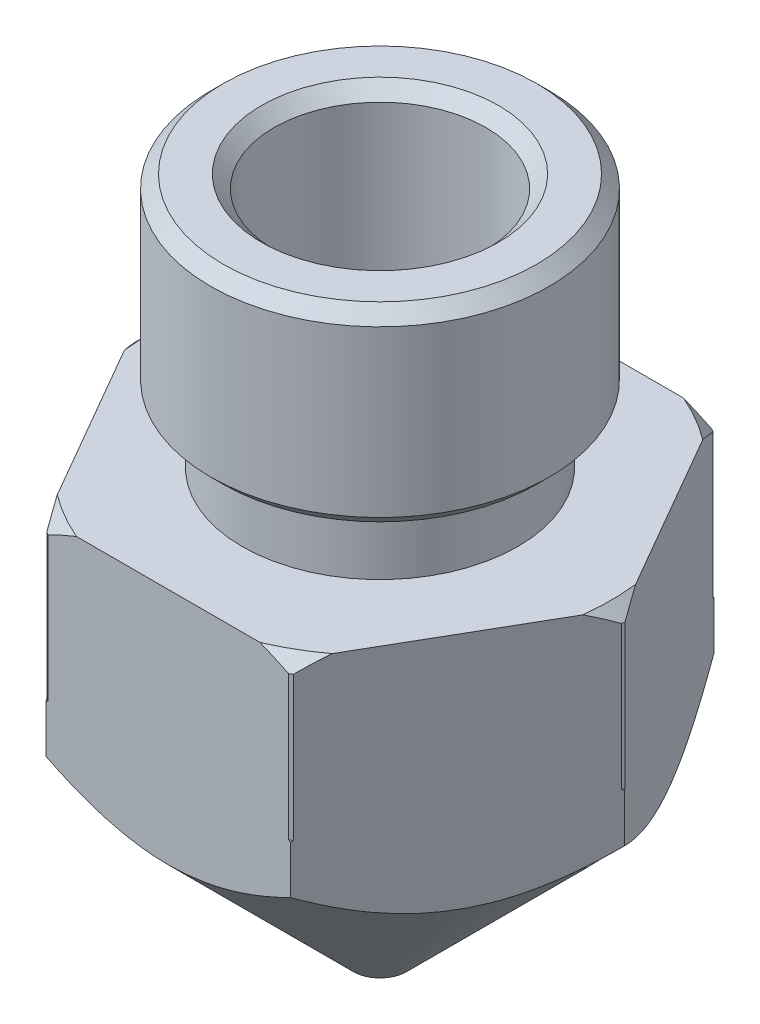
SolidWorks part; units mm, degrees
material "AISI 304"
ref_plane "Спереди" through (0, 0, 0) normal (0, 0, 1) x (1, 0, 0)
ref_plane "Сверху" through (0, 0, 0) normal (0, 1, 0) x (1, 0, 0)
ref_plane "Справа" through (0, 0, 0) normal (1, 0, 0) x (0, 0, -1)
ref_axis "ОсьX" through (-88.99, 0, 0) along (1, 0, 0)
ref_axis "ОсьZ" through (0, 55, 0) along (0, -1, 0)
ref_axis "ОсьY" through (0, 0, -88.99) along (0, 0, 1)
sketch "Эскиз1" plane through (0, 0, 0) normal (0, 0, 1) x (1, 0, 0)
  line L0 (0, 8.2669) -> (0, -10.3174) construction
  line L1 (2.5, 0) -> (4, 0)
  line L2 (4, 0) -> (4, -4.5)
  line L3 (4, -4.5) -> (3.25, -4.5)
  line L4 (3.25, -4.5) -> (3.25, -6)
  line L5 (3.25, -6) -> (5.75, -6)
  line L6 (5.75, -6) -> (5.75, -10)
  line L7 (5.75, -10) -> (6.6317, -10)
  line L8 (6.6317, -10) -> (0.6317, -16)
  line L9 (0.5, -15) -> (2.5, -12.6165)
  line L10 (2.5, -12.6165) -> (2.5, 0)
  line L11 (0.5, -15) -> (0.6317, -16)
  dimension "D1" = 5
  dimension "D2" = 1
  dimension "D3" = 7.5
  dimension "D4" = 1
  dimension "D5" = 8
  dimension "D6" = 6.5
  dimension "D7" = 6
  dimension "D8" = 1.5
  dimension "D9" = 11.5
  dimension "D10" = 4
  dimension "D11" = 45
  dimension "D12" = 40
  dimension "D13" = 6
revolve "Повернуть1" add sketch "Эскиз1" angle 360 mid plane about L0
cosmetic thread "Условное изображение резьбы1" parameters "D2"=6.917
chamfer "Фаска1" distance 0.3 angle 45 5 edges at (0, -10, 5.75) (0, -6, 5.75) (0, -4.5, 4) (0, 0, 2.5) (0, 0, 4)
sketch "Эскиз2" plane through (0, -6, 0) normal (0, 1, 0) x (1, 0, 0)
  line L1 (5.7735, 0) -> (2.8868, 5)
  line L2 (2.8868, 5) -> (-2.8868, 5)
  line L3 (-2.8868, 5) -> (-5.7735, 0)
  line L4 (-5.7735, 0) -> (-2.8868, -5)
  line L5 (-2.8868, -5) -> (2.8868, -5)
  line L6 (2.8868, -5) -> (5.7735, 0)
  circle A0 centre (0, 0) radius 5 construction
  dimension "D1" = 10
extrude "Вырез-Вытянуть1" cut sketch "Эскиз2" against normal through all flip side to cut
